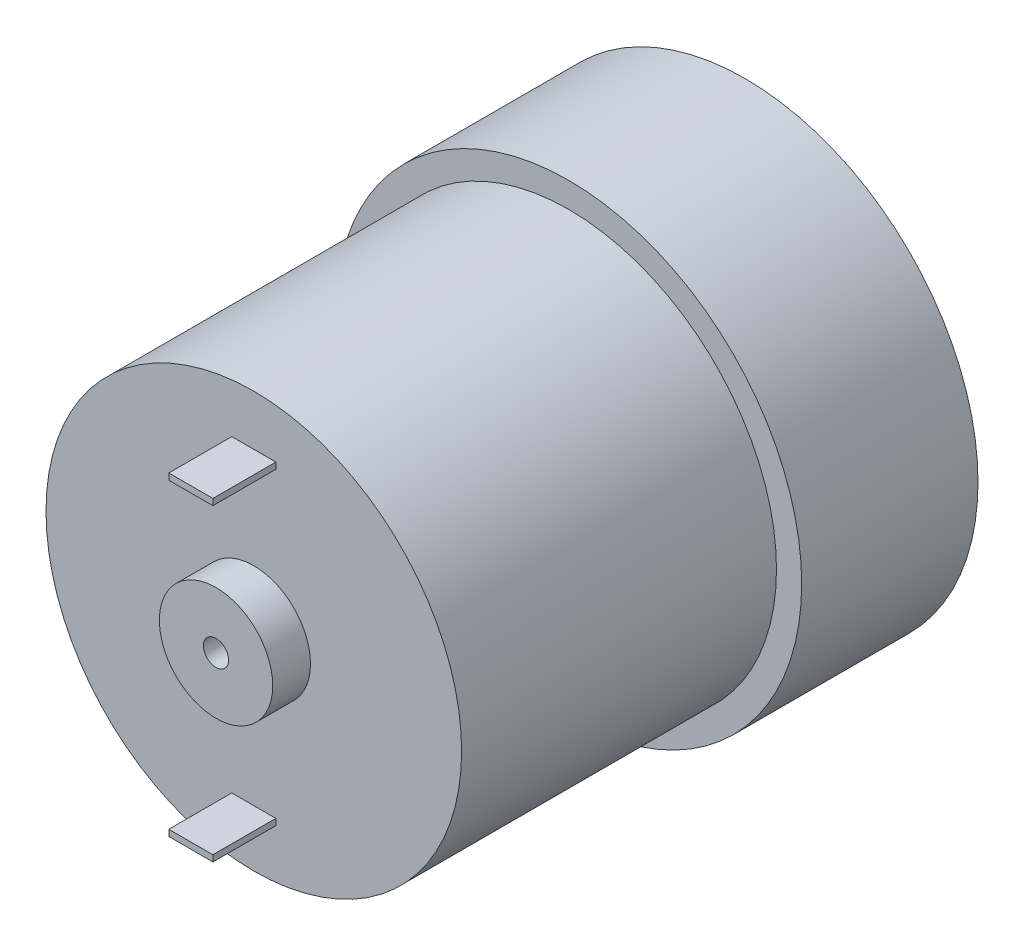
SolidWorks part; units mm, degrees
material "6063-O"
ref_plane "Front Plane" through (0, 0, 0) normal (0, 0, 1) x (1, 0, 0)
ref_plane "Top Plane" through (0, 0, 0) normal (0, 1, 0) x (1, 0, 0)
ref_plane "Right Plane" through (0, 0, 0) normal (1, 0, 0) x (0, 0, -1)
sketch "Sketch1" plane through (0, 0, 0) normal (0, 0, 1) x (1, 0, 0)
  circle A0 centre (0, 0) radius 18.5
  dimension "D1" = 37
extrude "Boss-Extrude1" add sketch "Sketch1" along normal blind 42
sketch "Sketch2" plane through (0, 0, 42) normal (0, 0, 1) x (1, 0, 0)
  circle A0 centre (0, 0) radius 18.5
  circle A1 centre (0, 0) radius 18.5 construction
  circle A2 centre (0, 0) radius 4.5
  dimension "D1" = 9
extrude "Cut-Extrude1" cut sketch "Sketch2" against normal blind 3
sketch "Sketch3" plane through (0, 0, 39) normal (0, 0, 1) x (1, 0, 0)
  circle A0 centre (0, 0) radius 18.5
  circle A1 centre (0, 0) radius 18.5 construction
  circle A2 centre (0, 0) radius 16.5
  circle M4 centre (0, 0) radius 18.5
  dimension "D1" = 33
extrude "Cut-Extrude4" cut sketch "Sketch3" against normal blind 25 contours A2 M4 region at (-17.9767, 0, 39)
sketch "Sketch4" plane through (0, 0, 0) normal (0, 0, -1) x (-1, 0, 0)
  line L0 (0, 0) -> (0, -18.5) construction
  circle A0 centre (0, 0) radius 18.5 construction
  circle A1 centre (0, -7) radius 6
  dimension "D2" = 12
  dimension "D1" = 7
extrude "Boss-Extrude2" add sketch "Sketch4" along normal blind 4.6
fillet "Fillet1" radius 0.5 1 edges at (-6, -7, -4.6)
sketch "Sketch5" plane through (0, 0, -4.6) normal (0, 0, -1) x (-1, 0, 0)
  circle A0 centre (0, -7) radius 3
  dimension "D1" = 6
extrude "Cut-Extrude5" cut sketch "Sketch5" against normal blind 10
sketch "Sketch6" plane through (0, 0, 42) normal (0, 0, 1) x (1, 0, 0)
  circle A0 centre (0, 0) radius 1
  dimension "D1" = 2
extrude "Cut-Extrude6" cut sketch "Sketch6" against normal blind 10
sketch "Sketch7" plane through (0, 0, 39) normal (0, 0, 1) x (1, 0, 0)
  line L0 (0, -16.5) -> (0, 16.5) construction
  line L2 (1.75, 12) -> (-1.75, 12)
  line L3 (1.75, 12) -> (1.75, 12.5)
  line L4 (1.75, 12.5) -> (-1.75, 12.5)
  line L5 (-1.75, 12) -> (-1.75, 12.5)
  line L6 (1.75, 12) -> (-1.75, 12.5) construction
  line L7 (1.75, 12.5) -> (-1.75, 12) construction
  line L8 (-1.75, -12) -> (1.75, -12)
  line L9 (-1.75, -12) -> (-1.75, -12.5)
  line L10 (-1.75, -12.5) -> (1.75, -12.5)
  line L11 (1.75, -12) -> (1.75, -12.5)
  line L12 (-1.75, -12) -> (1.75, -12.5) construction
  line L13 (-1.75, -12.5) -> (1.75, -12) construction
  circle A0 centre (0, 0) radius 16.5 construction
  point P5 (0, 12.25)
  point P10 (0, -12.25)
  dimension "D1" = 3.5
  dimension "D2" = 0.5
  dimension "D3" = 12
  dimension "D4" = 12
extrude "Boss-Extrude3" add sketch "Sketch7" along normal blind 5
sketch "Sketch8" plane through (0, 0, 0) normal (0, 0, -1) x (-1, 0, 0)
  line L0 (0, 0) -> (15.5, 0) construction
  line L1 (0, 0) -> (-15.5, 0) construction
  line L2 (0, 0) -> (-7.75, 13.4234) construction
  line L3 (0, 0) -> (-7.75, -13.4234) construction
  line L4 (-13.8293, -7) -> (13.8293, -7) construction
  circle A0 centre (0, 0) radius 15.5 construction
  circle A1 centre (-7.75, 13.4234) radius 1.5
  circle A2 centre (15.5, 0) radius 1.75
  circle A3 centre (-7.75, -13.4234) radius 1.5
  circle A4 centre (-13.8293, -7) radius 1.5
  circle A5 centre (-15.5, 0) radius 1.75
  circle A6 centre (13.8293, -7) radius 1.5
  circle A7 centre (0, 15.5) radius 1.75
  point P15 (0, -7)
  dimension "D1" = 31
  dimension "D4" = 3
  dimension "D5" = 3.5
  dimension "D2" = 120
  dimension "D3" = 120
hole_wizard "M3x0.5 Tapped Hole1" positions "Sketch9" profile "Sketch10" tap size "M3x0.5" standard "ANSI Metric"
sketch "Sketch9" plane through (0, 0, 0) normal (0, 0, -1) x (-1, 0, 0)
  point P17 (15.5, 0)
  point P20 (-7.75, 13.4234)
  point P23 (-7.75, -13.4234)
  point P26 (-15.5, 0)
sketch "Sketch10" plane through (-15.5, 0, 0) normal (1, 0, 0) x (0, 1, 0)
  line L0 (0, 0) -> (0, 8.2511)
  line L1 (0, 8.2511) -> (1.25, 7.5)
  line L2 (1.25, 7.5) -> (1.25, 0)
  line L5 (1.25, 0) -> (0, 0)
  line L10 (0, 8.2511) -> (-1.25, 7.5) construction
  line L11 (0, -6.35) -> (0, 107.95) construction
  dimension "Tap Drill Dia." = 2.5
  dimension "Tap Drill Depth" = 7.5
  dimension "Drill Angle" = 118
cosmetic thread "Hole Thread1" parameters "D1"=6, "D2"=3
cosmetic thread "Hole Thread2" parameters "D1"=6, "D2"=3
cosmetic thread "Hole Thread3" parameters "D1"=6, "D2"=3
cosmetic thread "Hole Thread4" parameters "D1"=6, "D2"=3
hole_wizard "Ø3.0mm Dowel Hole1" positions "Sketch11" profile "Sketch12" hole size "Ø3.0" standard "ANSI Metric"
sketch "Sketch11" plane through (0, 0, 0) normal (0, 0, -1) x (-1, 0, 0)
  point P3 (0, 15.5)
  point P12 (-13.8293, -7)
  point P15 (13.8293, -7)
sketch "Sketch12" plane through (0, 15.5, 0) normal (1, 0, 0) x (0, 1, 0)
  line L0 (0, 0) -> (0, 8.4013)
  line L1 (0, 8.4013) -> (1.5, 7.5)
  line L2 (1.5, 7.5) -> (1.5, 0)
  line L5 (1.5, 0) -> (0, 0)
  line L10 (0, 8.4013) -> (-1.5, 7.5) construction
  line L11 (0, -6.35) -> (0, 107.95) construction
  dimension "Hole Dia." = 3
  dimension "Hole Depth" = 7.5
  dimension "Drill Angle" = 118
equation "\"D4@Sketch7\"=\"D3@Sketch7\""
